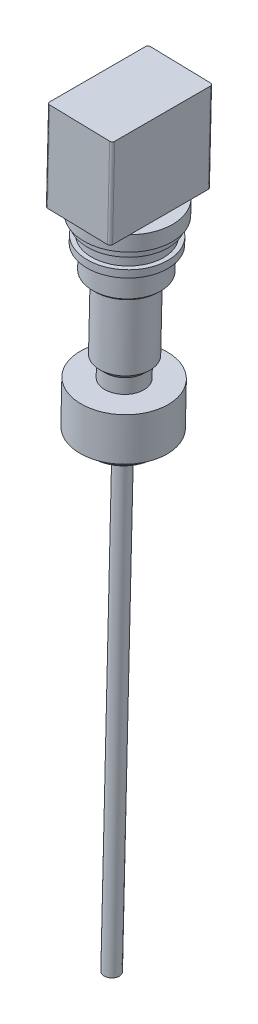
SolidWorks part; units mm, degrees
material "6061-T6 (SS)"
ref_plane "Front" through (0, 0, 0) normal (0, 0, 1) x (1, 0, 0)
ref_plane "Top" through (0, 0, 0) normal (0, 1, 0) x (1, 0, 0)
ref_plane "Right" through (0, 0, 0) normal (1, 0, 0) x (0, 0, -1)
sketch "Sketch1" plane through (0, 0, 0) normal (0, 0, 1) x (1, 0, 0)
  line L4 (0, 0) -> (0, 242.8932)
  line L5 (340.4001, 0) -> (353.2624, 536.8) construction
  line L6 (279.1618, 74.2828) -> (290.9941, 568.093)
  line L7 (290.9941, 568.093) -> (240.0087, 569.3146)
  line L8 (240.0087, 569.3146) -> (228.1765, 75.5045) construction
  line L9 (228.1765, 75.5045) -> (279.1618, 74.2828) construction
  line L10 (239.6933, 326.7526) -> (285.1852, 325.6626) construction
  line L11 (244.2699, 289.1803) -> (284.288, 288.2214) construction
  line L12 (340.4001, 0) -> (339.3876, -42.2576) construction
  line L13 (340.3833, -0.6998) -> (346.3816, -0.8435)
  line L14 (340.3833, -0.6998) -> (353.1186, 530.7962)
  line L15 (346.3816, -0.8435) -> (355.1165, 363.7004)
  line L17 (340.3833, -0.6998) -> (346.2618, -5.8435)
  line L18 (346.2618, -5.8435) -> (346.3816, -0.8435)
  line L19 (355.1165, 363.7004) -> (374.8608, 363.2273)
  line L20 (374.8608, 363.2273) -> (375.0764, 372.2247)
  line L21 (375.0764, 372.2247) -> (383.8239, 372.0151)
  line L22 (383.8239, 372.0151) -> (384.6384, 406.0054)
  line L23 (384.6384, 406.0054) -> (365.6438, 406.4605)
  line L24 (365.6438, 406.4605) -> (365.9073, 417.4573)
  line L25 (365.9073, 417.4573) -> (370.406, 417.3496)
  line L26 (370.406, 417.3496) -> (371.8672, 478.332)
  line L27 (371.8672, 478.332) -> (378.8652, 478.1644)
  line L28 (378.8652, 478.1644) -> (379.3443, 498.1586)
  line L29 (379.3443, 498.1586) -> (384.3429, 498.0389)
  line L30 (384.3429, 498.0389) -> (384.4794, 503.7372)
  line L31 (384.4794, 503.7372) -> (380.9804, 503.8211)
  line L32 (380.9804, 503.8211) -> (381.1864, 512.4186)
  line L33 (381.1864, 512.4186) -> (384.6854, 512.3348)
  line L34 (384.6854, 512.3348) -> (384.822, 518.0331)
  line L35 (384.822, 518.0331) -> (387.8211, 517.9613)
  line L36 (387.8211, 517.9613) -> (388.1085, 529.9578)
  line L37 (388.1085, 529.9578) -> (353.1186, 530.7962)
  circle A0 centre (244.2699, 289.1803) radius 4
  circle A1 centre (239.6933, 326.7526) radius 4
  circle A2 centre (340.4001, 0) radius 5.3016 construction
  point P42 (264.279, 288.7009)
  dimension "D5" = 8
  dimension "D7" = 289.1803
  dimension "D1" = 244.2699
  dimension "D2" = 239.6933
  dimension "D3" = 25.75
  dimension "D4" = 326.7526
  dimension "D6" = 340.4001
  dimension "D8" = 9
  dimension "D9" = 242.5
  dimension "D10" = 51
  dimension "D11" = 214
  dimension "D12" = 0.7
  dimension "D13" = 6
  dimension "D14" = 5
  dimension "D15" = 369.65
  dimension "D16" = 34.5
  dimension "D17" = 34
  dimension "D18" = 15.5
  dimension "D19" = 11
  dimension "D20" = 20
  dimension "D21" = 61
  dimension "D22" = 27
  dimension "D23" = 20
  dimension "D24" = 32
  dimension "D25" = 5.7
  dimension "D26" = 28.5
  dimension "D27" = 32
  dimension "D28" = 5.7
  dimension "D29" = 20
  dimension "D30" = 35
  dimension "D31" = 12
revolve "Revolve2" add sketch "Sketch1" angle 360 about L14 region at (352.0872, 264.9203, 0)
chamfer "Chamfer1" distance 5 angle 45 1 edges at (370.406, 417.3496, 0)
chamfer "Chamfer2" distance 2 angle 45 2 edges at (378.8652, 478.1644, 0) (374.8608, 363.2273, 0)
sketch "Sketch2" plane through (12.9138, 538.9479, 0) normal (0.024, 0.9997, 0) x (0.9997, -0.024, 0)
  line L1 (365.8024, -39.5) -> (314.8024, -39.5)
  line L2 (365.8024, -39.5) -> (365.8024, 39.5)
  line L3 (365.8024, 39.5) -> (314.8024, 39.5)
  line L4 (314.8024, -39.5) -> (314.8024, 39.5)
  line L5 (365.8024, -39.5) -> (314.8024, 39.5) construction
  line L6 (365.8024, 39.5) -> (314.8024, -39.5) construction
  point P0 (340.3024, 0)
  dimension "D1" = 79
  dimension "D2" = 51
extrude "Boss-Extrude1" add sketch "Sketch2" along normal blind 71
fillet "Fillet1" radius 2 4 edges at (328.4763, 566.8969, -39.5) (379.4616, 565.6752, -39.5) (328.4763, 566.8969, 39.5) (379.4616, 565.6752, 39.5)
